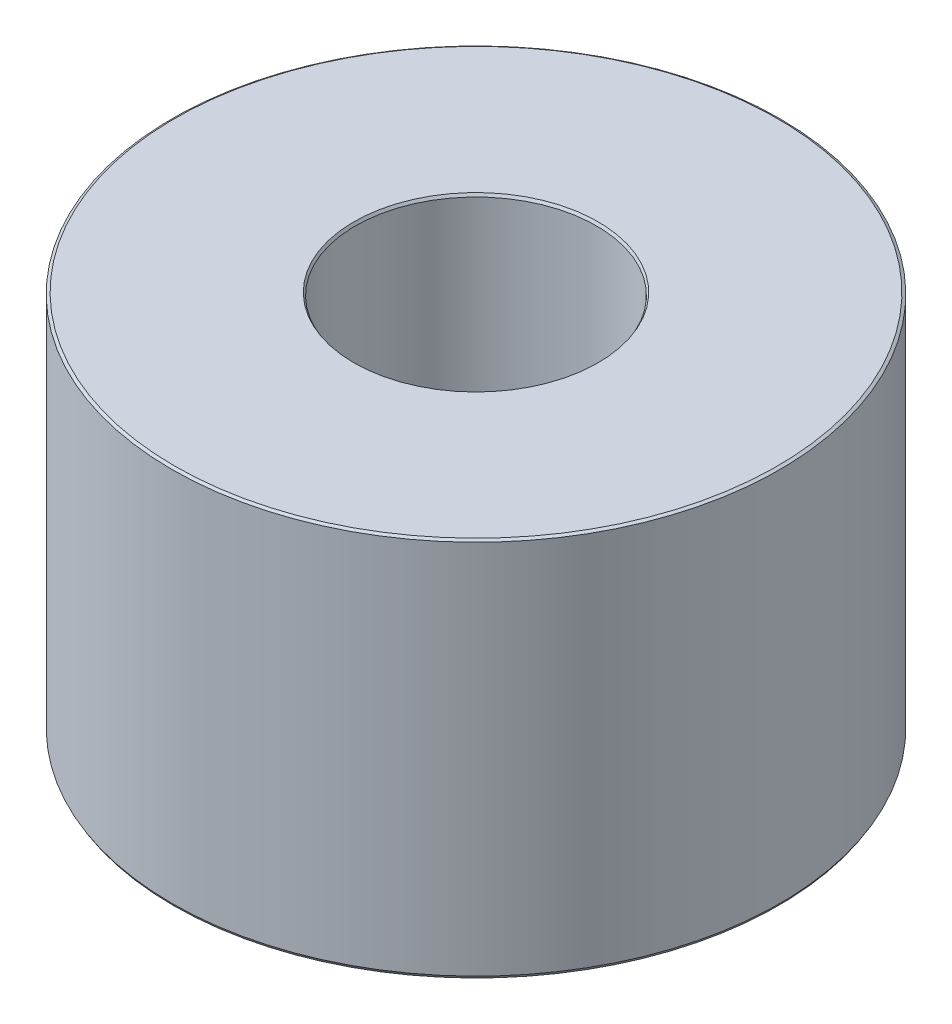
SolidWorks part; units mm, degrees
ref_plane "Front Plane" through (0, 0, 0) normal (0, 0, 1) x (1, 0, 0)
ref_plane "Top Plane" through (0, 0, 0) normal (0, 1, 0) x (1, 0, 0)
ref_plane "Right Plane" through (0, 0, 0) normal (1, 0, 0) x (0, 0, -1)
sketch "Sketch1" plane through (0, 0, 0) normal (0, 1, 0) x (1, 0, 0)
  circle A0 centre (0, 0) radius 42.5
  dimension "SLEEVE_OD" = 85
extrude "Boss-Extrude1" add sketch "Sketch1" along normal blind 53.1539
sketch "Sketch2" plane through (0, 0, 0) normal (0, 1, 0) x (1, 0, 0)
  circle A0 centre (0, 0) radius 16.8612
  dimension "BORE_D" = 33.7224
extrude "Cut-Extrude1" cut sketch "Sketch2" along normal through all
chamfer "Chamfer1" distance 0.2208 angle 60 4 edges at (0, 53.1539, 16.8612) (0, 0, 16.8612) (0, 0, 42.5) (0, 53.1539, 42.5) first distance on face at (0, 53.1539, 16.8612) first distance on face at (0, 0, 16.8612) first distance on face at (0, 53.1539, 42.5)
